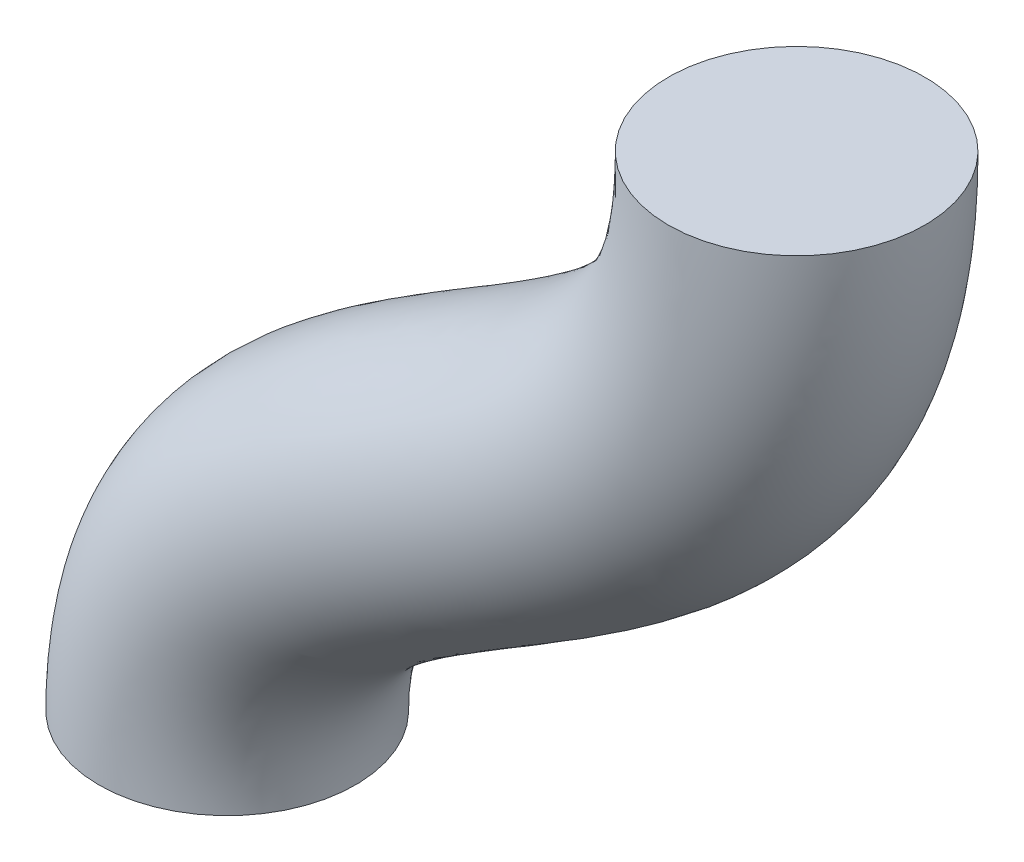
SolidWorks part; units mm, degrees
ref_plane "Front Plane" through (0, 0, 0) normal (0, 0, 1) x (1, 0, 0)
ref_plane "Top Plane" through (0, 0, 0) normal (0, 1, 0) x (1, 0, 0)
ref_plane "Right Plane" through (0, 0, 0) normal (1, 0, 0) x (0, 0, -1)
sketch "Sketch3" plane through (0, 0, 0) normal (0, 0, 1) x (1, 0, 0)
  line L1 (0, -15.0231) -> (0, 0) construction
  line L2 (-28.1908, -53.1231) -> (-28.1908, -70.2904) construction
  spline S0 degree 3 poles (-28.1908, -53.1231) (-28.1908, -44.4955) (-14.1936, -35.1056) (0, -27.5732) (0, -15.0231) knots 0 0 0 0 0.427174 1 1 1 1
  point P2 (1.0072, -7.9375)
  point P6 (0, 0)
  dimension "D1" = 38.1
  dimension "D2" = 15.0231
  dimension "D3" = 17.1673
  dimension "D4" = 11.9944
  dimension "D5" = 16.3109
  dimension "D6" = 28.1908
ref_plane "Plane1" through (0, -53.1231, 0) normal (0, 1, 0) x (1, 0, 0)
sketch "Sketch4" plane through (0, -53.1231, 0) normal (0, 1, 0) x (1, 0, 0)
  circle A0 centre (-28.1908, 0) radius 6.35
  dimension "D1" = 12.7
sweep "Sweep1" add profiles "Sketch4" path "Sketch3"
